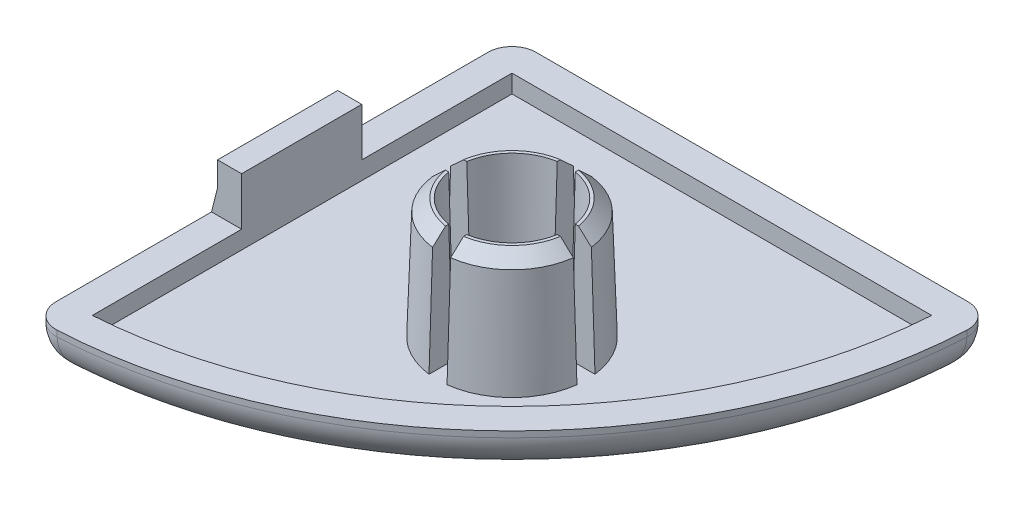
SolidWorks part; units mm, degrees
ref_plane "前视" through (0, 0, 0) normal (0, 0, 1) x (1, 0, 0)
ref_plane "上视" through (0, 0, 0) normal (0, 1, 0) x (1, 0, 0)
ref_plane "右视" through (0, 0, 0) normal (1, 0, 0) x (0, 0, -1)
sketch "草图1" plane through (0, 0, 0) normal (0, 1, 0) x (1, 0, 0)
  line L2 (-20, -20) -> (-20, 20)
  line L3 (-20, 20) -> (20, 20)
  line L5 (-20, -20) -> (20, 20) construction
  line L6 (-20, 20) -> (20, -20) construction
  arc A0 (-20, -20) -> (20, 20) centre (-20, 20) ccw
  point P0 (0, 0)
  dimension "D1" = 40
extrude "凸台-拉伸1" add sketch "草图1" along normal blind 3.5
sketch "草图2" plane through (0, 3.5, 0) normal (0, 1, 0) x (1, 0, 0)
  line L4 (17.4166, 17.5) -> (-17.5, 17.5)
  line L5 (-17.5, 17.5) -> (-17.5, -17.4166)
  line L6 (17.4166, 17.5) -> (-17.5, 17.5)
  line L7 (-17.5, 17.5) -> (-17.5, -17.4166)
  arc A2 (-17.5, -17.4166) -> (17.4166, 17.5) centre (-20, 20) ccw
  arc A3 (-17.5, -17.4166) -> (17.4166, 17.5) centre (-20, 20) ccw
  dimension "D1" = 2.5
extrude "切除-拉伸1" cut sketch "草图2" against normal blind 1.5
fillet "圆角1" radius 2 3 edges at (-20, 1.75, -20) (-20, 1.75, 20) (20, 1.75, -20)
fillet "圆角2" radius 3 6 edges at (-0.0263, 0, -20) (-19.4142, 0, -19.4142) (-20, 0, -0.0263) (8.2843, 0, 8.2843) (19.3983, 0, -19.3765) (-19.3765, 0, 19.3983)
sketch "草图3" plane through (0, 3.5, 0) normal (0, 1, 0) x (1, 0, 0)
  line L1 (-19.5, 5) -> (-17.5, 5)
  line L2 (-19.5, 5) -> (-19.5, -5)
  line L3 (-19.5, -5) -> (-17.5, -5)
  line L4 (-17.5, 5) -> (-17.5, -5)
  dimension "D2" = 10
  dimension "D3" = 2
extrude "凸台-拉伸2" add sketch "草图3" along normal blind 4
sketch "草图5" plane through (0, 0, 5) normal (0, 0, 1) x (1, 0, 0)
  line L0 (-19.5, 7.5) -> (-19.5, 3.5) construction
  line L1 (-20, 3.5) -> (-19.5, 3.5)
  line L2 (-19.5, 3.5) -> (-17.5, 3.5) construction
  line L4 (-19.5, 3.5) -> (-19.5, 5.5)
  line L5 (-19.5, 5.5) -> (-20, 3.5)
extrude "凸台-拉伸3" add sketch "草图5" against normal up to surface (10 mm away) up to face at (-18.25, 6, -5)
sketch "草图6" plane through (0, 2, 0) normal (0, 1, 0) x (1, 0, 0)
  circle A0 centre (0, 0) radius 6.2
  circle A1 centre (0, 0) radius 4.25
  dimension "D1" = 12.4
  dimension "D2" = 8.5
extrude "凸台-拉伸4" add sketch "草图6" along normal blind 10 draft 1.88
chamfer "倒角1" distance 1 angle 45 1 edges at (0, 12, 5.8718) first distance on face at (0, 12, 5.8718)
sketch "草图7" plane through (0, 12, 0) normal (0, 1, 0) x (1, 0, 0)
  line L1 (-0.75, -8.4649) -> (0.75, -8.4649)
  line L2 (-0.75, -8.4649) -> (-0.75, -0.75)
  line L3 (-0.75, 8.4649) -> (0.75, 8.4649)
  line L4 (0.75, -8.4649) -> (0.75, -0.75)
  line L7 (-8.6795, 0.75) -> (-0.75, 0.75)
  line L8 (-8.6795, 0.75) -> (-8.6795, -0.75)
  line L9 (-8.6795, -0.75) -> (-0.75, -0.75)
  line L10 (8.6795, 0.75) -> (8.6795, -0.75)
  line L13 (-0.75, 0.75) -> (-0.75, 8.4649)
  line L17 (0.75, 0.75) -> (0.75, 8.4649)
  line L19 (0.75, 0.75) -> (8.6795, 0.75)
  line L20 (0.75, -0.75) -> (8.6795, -0.75)
  point P0 (0, 0)
  point P6 (0, 0)
  dimension "D1" = 1.5
  dimension "D2" = 1.5
extrude "切除-拉伸2" cut sketch "草图7" against normal up to surface (10 mm away) up to face at (-3.6751, 2, -3.6751)
